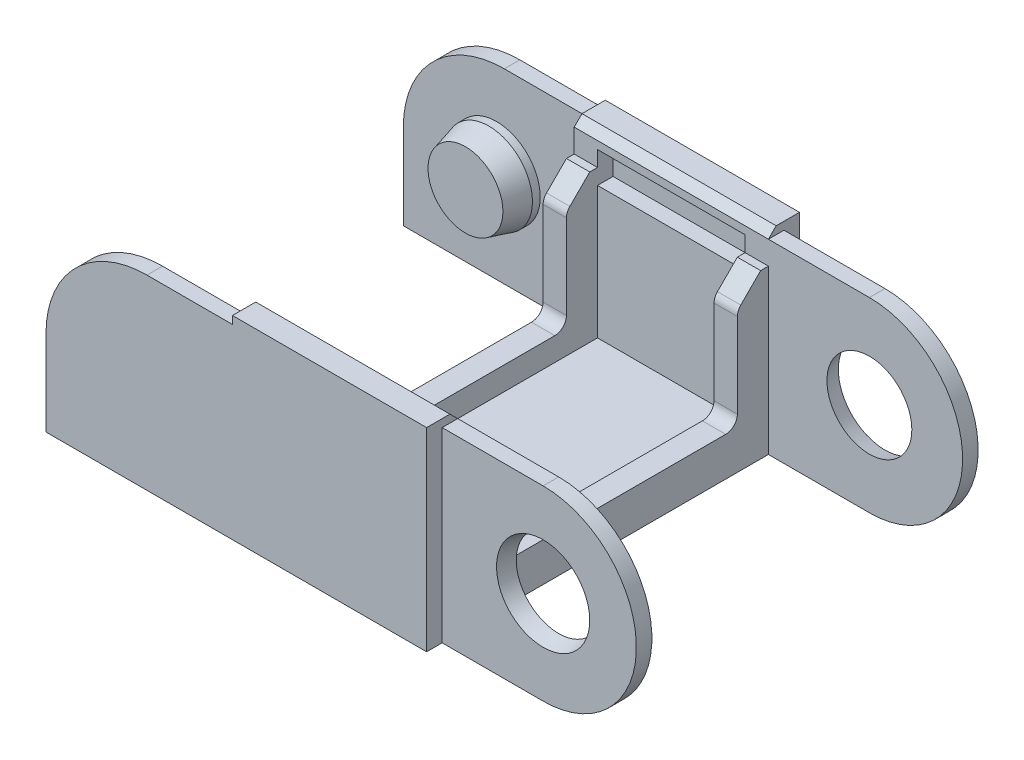
SolidWorks part; units mm, degrees
ref_plane "Front" through (0, 0, 0) normal (0, 0, 1) x (1, 0, 0)
ref_plane "Top" through (0, 0, 0) normal (0, 1, 0) x (1, 0, 0)
ref_plane "Right" through (0, 0, 0) normal (1, 0, 0) x (0, 0, -1)
sketch "Эскиз1" plane through (0, 0, 0) normal (0, 0, 1) x (1, 0, 0)
  line L1 (-38.7795, 23.7195) -> (-13.7795, 23.7195)
  line L2 (-38.7795, 23.7195) -> (-38.7795, -1.2805)
  line L3 (-38.7795, -1.2805) -> (-13.7795, -1.2805)
  line L4 (-13.7795, 23.7195) -> (-13.7795, -1.2805)
  dimension "D1" = 25
  dimension "D2" = 25
extrude "Бобышка-Вытянуть1" add sketch "Эскиз1" along normal blind 4
sketch "Эскиз2" plane through (0, 0, 0) normal (0, 0, -1) x (-1, 0, 0)
  line L0 (38.7795, 22.7195) -> (62.7795, 22.7195)
  line L1 (38.7795, 23.7195) -> (38.7795, -1.2805) construction
  line L3 (62.7795, 22.7195) -> (62.7795, -1.2805)
  line L4 (62.7795, -1.2805) -> (38.7795, -1.2805)
  line L5 (38.7795, -1.2805) -> (38.7795, 22.7195)
  dimension "D1" = 24
  dimension "D2" = 24
extrude "Бобышка-Вытянуть2" add sketch "Эскиз2" against normal blind 2
sketch "Эскиз3" plane through (0, 0, 2) normal (0, 0, 1) x (1, 0, 0)
  line L1 (-38.7795, -1.2805) -> (-62.7795, -1.2805) construction
  line L2 (-62.7795, -1.2805) -> (-62.7795, 22.7195) construction
  circle A0 centre (-50.7795, 10.7195) radius 5.625
  dimension "D2" = 11.25
  dimension "D1" = 12
  dimension "D3" = 12
extrude "Бобышка-Вытянуть3" add sketch "Эскиз3" along normal blind 4
chamfer "Фаска1" distance 3 angle 15 1 edges at (-45.1545, 10.7195, 6) first distance on face at (-45.1545, 10.7195, 6)
sketch "Эскиз4" plane through (0, 0, 6) normal (0, 0, 1) x (1, 0, 0)
  circle A1 centre (-50.7795, 10.7195) radius 13
  circle A4 centre (-50.7795, 10.7195) radius 7.5542
sketch "Эскиз5" plane through (0, 0, 4) normal (0, 0, 1) x (1, 0, 0)
  line L0 (-18.982, 10.7195) -> (-0.7795, 10.7195) construction
  line L1 (-18.982, 22.7195) -> (-0.7795, 22.7195)
  line L2 (-18.982, -1.2805) -> (-0.7795, -1.2805)
  line L3 (-13.7795, -1.2805) -> (-13.7795, 23.7195) construction
  line L4 (-38.7795, -1.2805) -> (-13.7795, -1.2805) construction
  arc A0 (-18.982, 22.7195) -> (-18.982, -1.2805) centre (-18.982, 10.7195) ccw
  arc A1 (-0.7795, -1.2805) -> (-0.7795, 22.7195) centre (-0.7795, 10.7195) ccw
  point P2 (-9.8808, 10.7195)
  dimension "D1" = 13
  dimension "D2" = 12
  dimension "D3" = 12
extrude "Бобышка-Вытянуть4" add sketch "Эскиз5" against normal blind 2
sketch "Эскиз6" plane through (0, 0, 2) normal (0, 0, -1) x (-1, 0, 0)
  circle A0 centre (0.7795, 10.7195) radius 5
  arc A1 (0.7795, 22.7195) -> (0.7795, -1.2805) centre (0.7795, 10.7195) ccw construction
extrude "Вырез-Вытянуть2" cut sketch "Эскиз6" against normal blind 10
sketch "Эскиз8" plane through (0, 0, 4) normal (0, 0, 1) x (1, 0, 0)
  line L5 (-38.7795, 3.7195) -> (-35.7795, 3.7195)
  line L6 (-38.7795, -1.2805) -> (-13.7795, -1.2805)
  line L7 (-38.7795, -1.2805) -> (-38.7795, 3.7195)
  line L9 (-13.7795, -1.2805) -> (-13.7795, 3.7195)
  line L10 (-35.7795, 3.7195) -> (-35.7795, 0.7195)
  line L11 (-35.7795, 0.7195) -> (-16.7795, 0.7195)
  line L12 (-16.7795, 0.7195) -> (-16.7795, 3.7195)
  line L13 (-16.7795, 3.7195) -> (-13.7795, 3.7195)
  line L14 (-13.7795, 22.7195) -> (-13.7795, 23.7195) construction
  dimension "D1" = 3
  dimension "D2" = 3
  dimension "D3" = 2
  dimension "D4" = 5
  dimension "D5" = 5
extrude "Бобышка-Вытянуть6" add sketch "Эскиз8" along normal blind 20
sketch "Эскиз9" plane through (0, 0, 4) normal (0, 0, 1) x (1, 0, 0)
  line L0 (-38.7795, 23.7195) -> (-38.7795, 3.7195) construction
  line L1 (-35.7795, 20.7195) -> (-16.7795, 20.7195)
  line L2 (-35.7795, 20.7195) -> (-35.7795, 17.7195)
  line L3 (-35.7795, 17.7195) -> (-16.7795, 17.7195)
  line L4 (-16.7795, 20.7195) -> (-16.7795, 17.7195)
  line L5 (-13.7795, 22.7195) -> (-13.7795, 23.7195) construction
  line L6 (-13.7795, 23.7195) -> (-38.7795, 23.7195) construction
  dimension "D1" = 3
  dimension "D2" = 3
  dimension "D3" = 3
  dimension "D4" = 6
extrude "Вырез-Вытянуть4" cut sketch "Эскиз9" against normal blind 2
chamfer "Фаска2" distance 1 angle 45 1 edges at (-26.2795, 20.7195, 4)
chamfer "Фаска3" distance 1 angle 75 1 edges at (-5.7795, 10.7195, 2) first distance on face at (-5.7795, 10.7195, 2)
fillet "Скругление1" radius 13 1 edges at (-62.7795, 22.7195, 1)
chamfer "Фаска4" distance 1 angle 45 1 edges at (-26.2795, 23.7195, 4)
sketch "Эскиз11" plane through (0, 3.7195, 0) normal (0, 1, 0) x (1, 0, 0)
  line L0 (-35.7795, -24) -> (-35.7795, -4) construction
  line L1 (-38.7795, -4) -> (-35.7795, -4)
  line L2 (-38.7795, -4) -> (-38.7795, -8)
  line L3 (-38.7795, -8) -> (-35.7795, -8)
  line L4 (-35.7795, -4) -> (-35.7795, -8)
  dimension "D1" = 4
extrude "Бобышка-Вытянуть7" add sketch "Эскиз11" along normal blind 16
pattern_linear "Линейный массив1" count 2 spacing 22 along (1, 0, 0) of "Бобышка-Вытянуть7"
chamfer "Фаска6" distance 3 angle 45 2 edges at (-15.2795, 19.7195, 8) (-37.2795, 19.7195, 8)
fillet "Скругление2" radius 1.5 4 edges at (-15.2795, 3.7195, 8) (-15.2795, 16.7195, 8) (-37.2795, 16.7195, 8) (-37.2795, 3.7195, 8)
mirror "Зеркальное отражение1" about plane through (0, 0, 24) normal (0, 0, -1) of bodies 113 109
